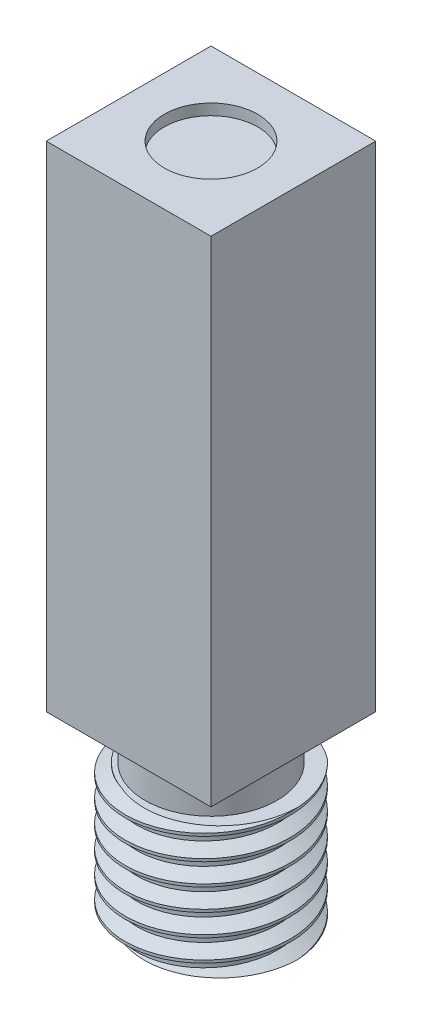
SolidWorks part; units mm, degrees
ref_plane "Piano frontale" through (0, 0, 0) normal (0, 0, 1) x (1, 0, 0)
ref_plane "Piano superiore" through (0, 0, 0) normal (0, 1, 0) x (1, 0, 0)
ref_plane "Piano destro" through (0, 0, 0) normal (1, 0, 0) x (0, 0, -1)
sketch "Schizzo1" plane through (0, 0, 0) normal (0, 1, 0) x (1, 0, 0)
  line L0 (0, 50.9857) -> (0, -54.0167) construction
  line L1 (-65.0582, 0) -> (55.7487, 0) construction
  line L3 (-7.5, 7.5) -> (7.5, 7.5)
  line L4 (-7.5, 7.5) -> (-7.5, -7.5)
  line L5 (-7.5, -7.5) -> (7.5, -7.5)
  line L6 (7.5, 7.5) -> (7.5, -7.5)
  line L7 (-7.5, 7.5) -> (7.5, -7.5) construction
  line L8 (-7.5, -7.5) -> (7.5, 7.5) construction
  point P5 (0, 0)
  dimension "D1" = 15
extrude "Estrusione-Estrusione1" add sketch "Schizzo1" along normal blind 45
sketch "Sketch1" plane through (0, 0, 0) normal (0, -1, 0) x (1, 0, 0)
  circle A0 centre (0, 0) radius 6
  dimension "D1" = 12
extrude "Boss-Extrude1" add sketch "Sketch1" along normal blind 4
sketch "Sketch11" plane through (0, -4, 0) normal (0, -1, 0) x (1, 0, 0)
  circle A0 centre (0, 0) radius 7.5
  dimension "D1" = 15
extrude "Boss-Extrude2" add sketch "Sketch11" along normal blind 12
thread "Thread2" pitch 2 method cut trim with start face yes trim with end face yes profile "Thread Profile2" start angle 3, offset 2, length 15, pitch 2, diameter 15
ref_plane "Plane6" through (7.4897, -18, -0.3925) normal (0.0523, 0, 0.9986) x (0.9986, 0, -0.0523)
sketch "Thread Profile2" plane through (7.4897, -18, -0.3925) normal (0.0523, 0, 0.9986) x (0.9986, 0, -0.0523)
  line L0 (0, 0) -> (0, 2) construction
  line L11 (0, 0) -> (0, 1.75)
  line L12 (0, 1.75) -> (-1.0825, 1.125)
  line L13 (-1.0825, 1.125) -> (-1.0825, 0.625)
  line L15 (-1.0825, 0.625) -> (0, 0)
  line L17 (-1.0825, 0.875) -> (0, 0.875) construction
  point P2 (0, 0)
  dimension "Pitch" = 2
  dimension "Profile_Angle" = 60
  dimension "Profile_Land" = 0.5
  dimension "Profile_Height" = 1.0825
sketch "Sketch12" plane through (0, 45, 0) normal (0, 1, 0) x (1, 0, 0)
  circle A0 centre (0, 0) radius 4.25
  dimension "D1" = 8.5
extrude "Cut-Extrude1" cut sketch "Sketch12" against normal blind 1
